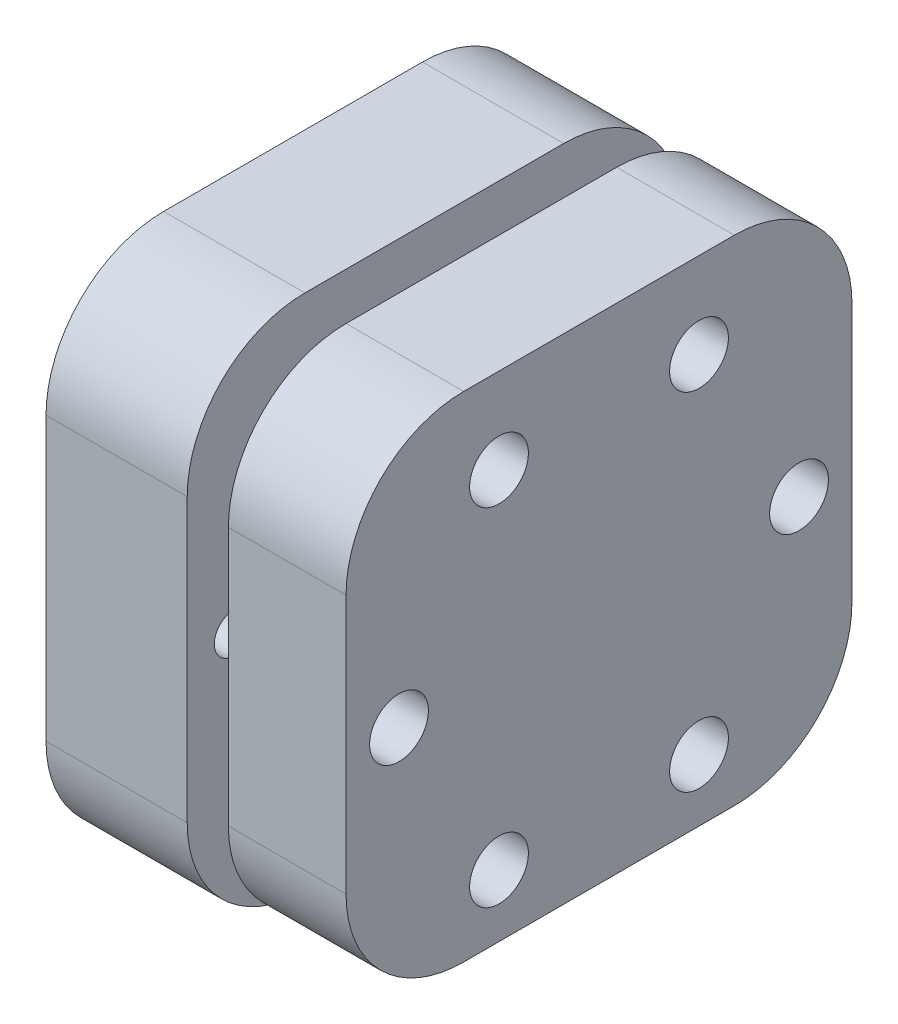
SolidWorks part; units mm, degrees
note: The reader was unsure of these and kept them because the rebuilt part matched: shared geometry of "Sketch5<3>", "Sketch5<12>", "Sketch5<13>", "Sketch5<15>".
other "Markup1"
sketch "Sketch6" plane through (0, 159.6749, -21.5) normal (0.919, 0.0758, -0.3869) x (-0.2653, -0.607, -0.7491)
ref_plane "Front Plane" through (0, 0, 0) normal (0, 0, 1) x (1, 0, 0)
ref_plane "Top Plane" through (0, 0, 0) normal (0, 1, 0) x (1, 0, 0)
ref_plane "Right Plane" through (0, 0, 0) normal (1, 0, 0) x (0, 0, -1)
sketch "Sketch2" plane through (0, 159.6749, 0) normal (0, -1, 0) x (1, 0, 0)
  line L1 (-10, 21.5) -> (0, 21.5)
  line L2 (0, 21.5) -> (0, -21.5)
  line L5 (-10, -21.5) -> (-10, 21.5)
  line L6 (0, -21.5) -> (-10, -21.5)
  line L7 (0, 0) -> (-10, 0) construction
  dimension "D1" = 10
  dimension "D2" = 43
extrude "Boss-Extrude1" add sketch "Sketch2" along normal blind 42
sketch "Sketch3" plane through (-10, 0, 0) normal (-1, 0, 0) x (0, 0, 1)
  line L0 (0, 138.6749) -> (0, 117.6749) construction
  line L1 (-12.5, 138.6749) -> (12.5, 138.6749)
  line L2 (-12.5, 138.6749) -> (-12.5, 129.6749)
  line L3 (-12.5, 129.6749) -> (12.5, 129.6749)
  line L4 (12.5, 138.6749) -> (12.5, 129.6749)
  line L8 (-17.8858, 117.6749) -> (16.2834, 117.6749) construction
  line L9 (21.5, 117.6749) -> (-21.5, 117.6749) construction
  dimension "D1" = 9
  dimension "D2" = 25
  dimension "D3" = 12
extrude "Boss-Extrude2" add sketch "Sketch3" along normal blind 4 contours L2 L3 L4 L1
sketch "Sketch5" plane through (-14, 0, 0) normal (-1, 0, 0) x (0, 0, 1)
  line L1 (0, 154.6749) -> (0, 137.6749) construction
  line L2 (21, 159.6749) -> (-21, 159.6749)
  line L3 (21, 159.6749) -> (21, 115.6749)
  line L4 (21, 115.6749) -> (-21, 115.6749)
  line L5 (-21, 159.6749) -> (-21, 115.6749)
  line L7 (0, 137.6749) -> (17, 137.6749) construction
  circle A0 centre (0, 137.6749) radius 17 construction
  circle A4 centre (17, 137.6749) radius 1.7
  circle A5 centre (17, 137.6749) radius 2.5
  circle A6 centre (17, 137.6749) radius 3
  circle A7 centre (8.5, 122.9524) radius 1.7
  circle A8 centre (8.5, 122.9524) radius 2.5
  circle A9 centre (8.5, 122.9524) radius 3
  circle A10 centre (-8.5, 122.9524) radius 1.7
  circle A11 centre (-8.5, 122.9524) radius 2.5
  circle A12 centre (-8.5, 122.9524) radius 3
  circle A13 centre (-17, 137.6749) radius 1.7
  circle A14 centre (-17, 137.6749) radius 2.5
  circle A15 centre (-17, 137.6749) radius 3
  circle A16 centre (-8.5, 152.3973) radius 1.7
  circle A17 centre (-8.5, 152.3973) radius 2.5
  circle A18 centre (-8.5, 152.3973) radius 3
  circle A19 centre (8.5, 152.3973) radius 1.7
  circle A20 centre (8.5, 152.3973) radius 2.5
  circle A21 centre (8.5, 152.3973) radius 3
  point P37 (0, 137.6749)
  point P41 (0, 137.6749)
  dimension "D1" = 34
  dimension "D2" = 3.4
  dimension "D3" = 5
  dimension "D4" = 6
  dimension "D9" = 137.6749
  dimension "D5" = 6
  dimension "D6" = 42
  dimension "D7" = 44
extrude "Boss-Extrude3" add sketch "Sketch5" along normal blind 12 separate body
extrude "Cut-Extrude1" cut sketch "Sketch5<3>" against normal blind 20 contours A16 | A17 A16 | A18 A17 | A19 | A20 A19 | A21 A20 | A6 A5 | A5 A4 | A4 | A15 A14 | A14 A13 | A13 | A12 A11 | A11 A10 | A10 | A9 A8 | A8 A7 | A7
sketch "Sketch5<3>" plane through (-14, 0, 0) normal (-1, 0, 0) x (0, 0, 1) same geometry as "Sketch5"
extrude "Boss-Extrude4" add sketch "Sketch5<12>" against normal offset from surface (6 mm away) 4 from surface at -4 contours A21 A20 | A18 A17 | A6 A5 | A9 A8 | A12 A11 | A15 A14 | A20 A19 | A5 A4 | A8 A7 | A11 A10 | A14 A13 | A17 A16 up to face at (0, 152.3973, -5.5) starting at face at (-10, 152.3973, -11.5)
sketch "Sketch5<12>" plane through (-14, 0, 0) normal (-1, 0, 0) x (0, 0, 1) same geometry as "Sketch5"
extrude "Boss-Extrude5" add sketch "Sketch5<13>" against normal up to surface (4 mm away) from surface at -10 contours A21 A20 | A18 A17 | A15 A14 | A12 A11 | A9 A8 | A6 A5 up to face at (0, 152.3973, -5.5) starting at face at (-4, 152.3973, 10.2)
sketch "Sketch5<13>" plane through (-14, 0, 0) normal (-1, 0, 0) x (0, 0, 1) same geometry as "Sketch5"
extrude "Boss-Extrude6" add sketch "Sketch5<15>" along normal up to surface (12 mm away) contours A17 A16 | A18 A17 | A14 A13 | A15 A14 | A11 A10 | A12 A11 | A9 A8 | A8 A7 | A20 A19 | A21 A20 | A5 A4 | A6 A5 up to face at (-26, 152.3973, 11.5)
sketch "Sketch5<15>" plane through (-14, 0, 0) normal (-1, 0, 0) x (0, 0, 1) same geometry as "Sketch5"
fillet "Fillet1" radius 10 8 edges at (-5, 159.6749, 21.5) (-5, 159.6749, -21.5) (-5, 117.6749, -21.5) (-5, 117.6749, 21.5) (-20, 115.6749, 21) (-20, 115.6749, -21) (-20, 159.6749, -21) (-20, 159.6749, 21)
